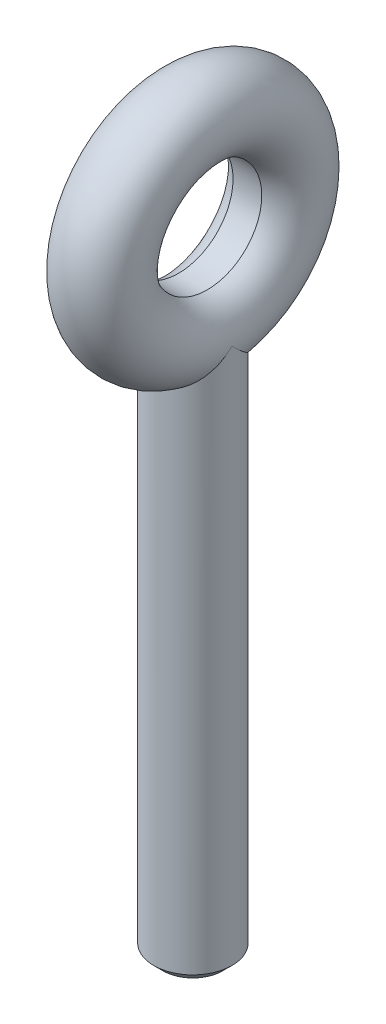
SolidWorks part; units mm, degrees
ref_plane "Plano frontal" through (0, 0, 0) normal (0, 0, 1) x (1, 0, 0)
ref_plane "Plano superior" through (0, 0, 0) normal (0, 1, 0) x (1, 0, 0)
ref_plane "Plano direito" through (0, 0, 0) normal (1, 0, 0) x (0, 0, -1)
sketch "Argola" plane through (0, 0, 0) normal (1, 0, 0) x (0, 0, -1)
  circle A0 centre (0, 0) radius 5
  point P6 (0, 0)
  dimension "D2" = 10
sweep "Varredura da Argola" add path "Argola" circular profile diameter 4.3 parameters "D3"=4.3
sketch "Pino" plane through (0, 0, 0) normal (1, 0, 0) x (0, 0, -1)
  line L0 (0, -5) -> (0, -35)
  circle A0 centre (0, 0) radius 5 construction
  dimension "D1" = 30
sweep "Varredura do Pino" add path "Pino" circular profile diameter 4.3 parameters "D3"=4.3
chamfer "Chanfro do pino" distance 0.5 angle 45 1 edges at (0, -35, -2.15)
sketch "Esboço1" plane through (0, 0, 0) normal (1, 0, 0) x (0, 0, -1)
  circle A0 centre (0, 0) radius 2.85 construction
  circle A1 centre (0, 0) radius 2.85
  circle A2 centre (0, 0) radius 3
  dimension "D1" = 6
extrude "Corte-extrusão1" cut sketch "Esboço1" against normal through all both and the other way through all
